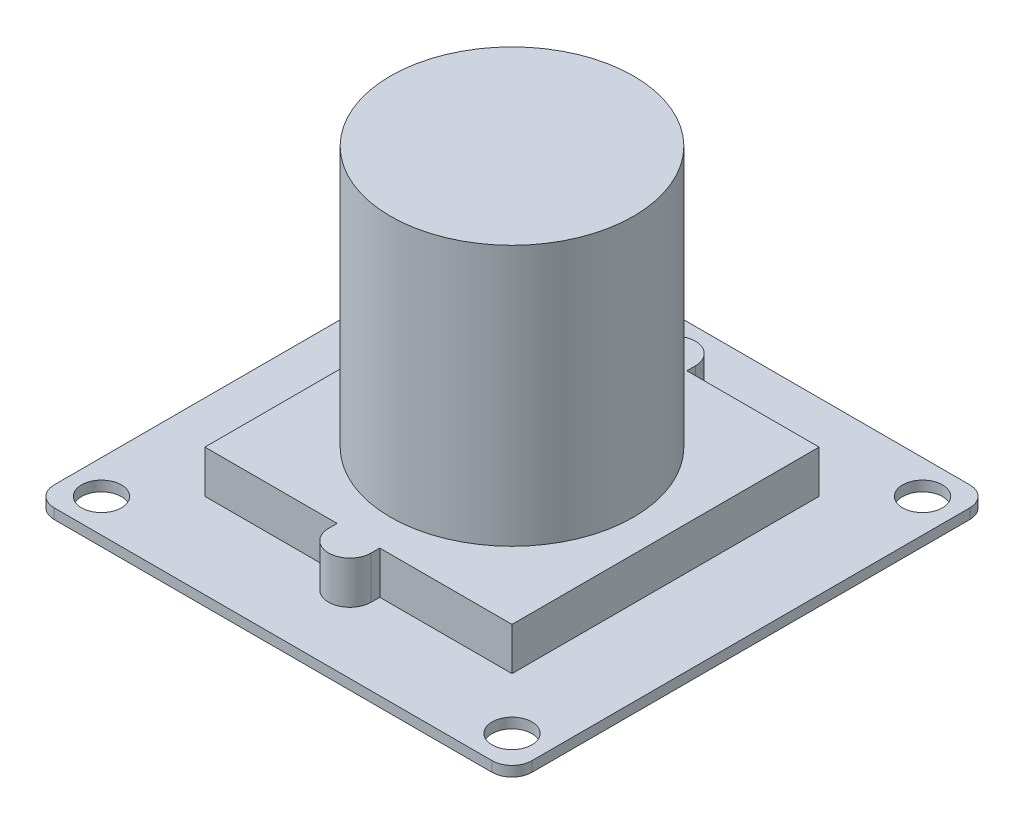
SolidWorks part; units mm, degrees
ref_plane "Front Plane" through (0, 0, 0) normal (0, 0, 1) x (1, 0, 0)
ref_plane "Top Plane" through (0, 0, 0) normal (0, 1, 0) x (1, 0, 0)
ref_plane "Right Plane" through (0, 0, 0) normal (1, 0, 0) x (0, 0, -1)
sketch "Sketch1" plane through (0, 0, 0) normal (0, 1, 0) x (1, 0, 0)
  line L1 (-16, -16) -> (16, -16)
  line L2 (-16, -16) -> (-16, 16)
  line L3 (-16, 16) -> (16, 16)
  line L4 (16, -16) -> (16, 16)
  line L5 (-16, -16) -> (16, 16) construction
  line L6 (-16, 16) -> (16, -16) construction
  point P0 (0, 0)
  dimension "D1" = 32
  dimension "D2" = 32
extrude "Boss-Extrude1" add sketch "Sketch1" along normal blind 0.681
sketch "Sketch2" plane through (0, 0.681, 0) normal (0, 1, 0) x (1, 0, 0)
  line L0 (16, 16) -> (16, 13.75) construction
  line L1 (16, -16) -> (16, 16) construction
  line L2 (16, 13.75) -> (13.75, 13.75) construction
  line L3 (-16, 16) -> (-16, 13.75) construction
  line L4 (-16, 16) -> (-16, -16) construction
  line L5 (16, -16) -> (13.75, -16) construction
  line L6 (-16, -16) -> (16, -16) construction
  line L7 (13.75, -16) -> (13.75, -13.75) construction
  line L8 (-16, -16) -> (-16, -13.75) construction
  line L9 (-16, -13.75) -> (-13.75, -13.75) construction
  line L10 (-16, 13.75) -> (-13.75, 13.75) construction
  circle A0 centre (13.75, 13.75) radius 1.3335
  circle A1 centre (-13.75, 13.75) radius 1.3335
  circle A2 centre (-13.75, -13.75) radius 1.3335
  circle A3 centre (13.75, -13.75) radius 1.3335
  dimension "D3" = 2.667
  dimension "D6" = 2.667
  dimension "D7" = 2.667
  dimension "D8" = 2.667
  dimension "D1" = 2.25
  dimension "D2" = 2.25
  dimension "D4" = 2.25
  dimension "D5" = 2.25
extrude "Cut-Extrude1" cut sketch "Sketch2" against normal blind 1
fillet "Fillet1" radius 1.335 4 edges at (16, 0.3405, -16) (16, 0.3405, 16) (-16, 0.3405, 16) (-16, 0.3405, -16)
sketch "Sketch3" plane through (0, 0.681, 0) normal (0, 1, 0) x (1, 0, 0)
  line L0 (0, 16) -> (0, 10.857) construction
  line L1 (-10.285, -10.285) -> (10.285, -10.285)
  line L2 (-10.285, -10.285) -> (-10.285, 10.285)
  line L3 (-10.285, 10.285) -> (10.285, 10.285)
  line L4 (10.285, -10.285) -> (10.285, 10.285)
  line L5 (-10.285, -10.285) -> (10.285, 10.285) construction
  line L6 (-10.285, 10.285) -> (10.285, -10.285) construction
  line L8 (14.665, 16) -> (-14.665, 16) construction
  line L9 (0, 10.857) -> (1.4285, 10.857) construction
  line L10 (0, 10.857) -> (-1.4285, 10.857) construction
  line L11 (1.4285, 10.857) -> (1.4285, 10.285)
  line L12 (-1.4285, 10.857) -> (-1.4285, 10.285)
  line L13 (0, -16) -> (0, -10.857) construction
  line L14 (-14.665, -16) -> (14.665, -16) construction
  line L15 (0, -10.857) -> (-1.4285, -10.857) construction
  line L16 (0, -10.857) -> (1.4285, -10.857) construction
  line L17 (-1.4285, -10.857) -> (-1.4285, -10.285)
  line L18 (1.4285, -10.857) -> (1.4285, -10.285)
  circle A0 centre (0, 10.857) radius 1.4285
  circle A1 centre (0, -10.857) radius 1.4285
  point P0 (0, 0)
  dimension "D3" = 5.143
  dimension "D4" = 2.857
  dimension "D1" = 20.57
  dimension "D2" = 20.57
  dimension "D5" = 5.143
extrude "Boss-Extrude2" add sketch "Sketch3" along normal blind 2.857 contours A1 L1 L4 L3 A0 L2 | L1 A1 | A1 L1 | A1 L18 L1 | A1 L1 L17 | L3 A0 | L3 A0 | A0 L3 L11 | A0 L12 L3 | A1 region at (0, 0.681, 0) region at (-1.3929, 0.681, 10.4268) region at (0, 0.681, 9.9317) region at (0, 0.681, 11.1688) region at (-1.3929, 0.681, -10.4268) region at (1.3929, 0.681, 10.4268) region at (0, 0.681, -11.1688) region at (0, 0.681, -9.9317) region at (1.3929, 0.681, -10.4268)
sketch "Sketch4" plane through (0, 3.538, 0) normal (0, 1, 0) x (1, 0, 0)
  circle A0 centre (0, 0) radius 8.1405
  dimension "D1" = 16.281
extrude "Boss-Extrude3" add sketch "Sketch4" along normal blind 17.46
